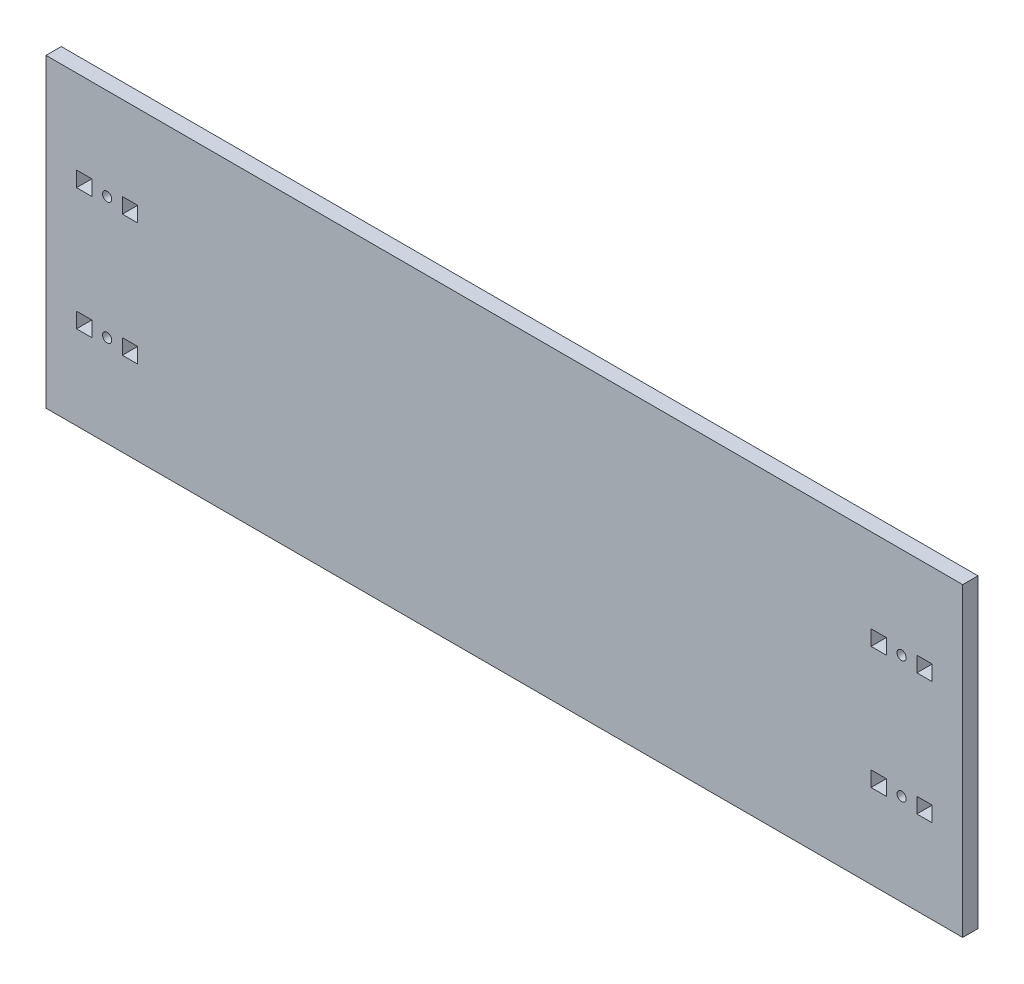
SolidWorks part; units mm, degrees
ref_plane "Front Plane" through (0, 0, 0) normal (0, 0, 1) x (1, 0, 0)
ref_plane "Top Plane" through (0, 0, 0) normal (0, 1, 0) x (1, 0, 0)
ref_plane "Right Plane" through (0, 0, 0) normal (1, 0, 0) x (0, 0, -1)
sketch "Sketch2" plane through (0, 0, 0) normal (0, 0, 1) x (1, 0, 0)
  line L0 (0, 50) -> (300, 50) construction
  line L1 (0, 0) -> (300, 0)
  line L2 (0, 0) -> (0, 100)
  line L3 (0, 100) -> (300, 100)
  line L4 (300, 0) -> (300, 100)
  point P7 (24.4287, 80.3835)
  point P8 (0, 0)
  point P9 (278.3505, 25.351)
  line B0 (15, 70) -> (25, 70) construction
  line B1 (15, 72.5) -> (10, 72.5)
  line B2 (15, 72.5) -> (15, 67.5)
  line B3 (15, 67.5) -> (10, 67.5)
  line B4 (10, 72.5) -> (10, 67.5)
  line B5 (25, 72.5) -> (30, 72.5)
  line B6 (25, 72.5) -> (25, 67.5)
  line B7 (25, 67.5) -> (30, 67.5)
  line B8 (30, 72.5) -> (30, 67.5)
  line B9 (20, 70) -> (20, 76.9724) construction
  circle B10 centre (20, 70) radius 1.5
  line B11 (275, 30) -> (285, 30) construction
  line B12 (275, 32.5) -> (270, 32.5)
  line B13 (275, 32.5) -> (275, 27.5)
  line B14 (275, 27.5) -> (270, 27.5)
  line B15 (270, 32.5) -> (270, 27.5)
  line B16 (285, 32.5) -> (290, 32.5)
  line B17 (285, 32.5) -> (285, 27.5)
  line B18 (285, 27.5) -> (290, 27.5)
  line B19 (290, 32.5) -> (290, 27.5)
  circle B20 centre (280, 30) radius 1.5
  line B21 (15, 30) -> (25, 30) construction
  line B22 (15, 27.5) -> (10, 27.5)
  line B23 (15, 27.5) -> (15, 32.5)
  line B24 (15, 32.5) -> (10, 32.5)
  line B25 (10, 27.5) -> (10, 32.5)
  line B26 (25, 27.5) -> (30, 27.5)
  line B27 (25, 27.5) -> (25, 32.5)
  line B28 (25, 32.5) -> (30, 32.5)
  line B29 (30, 27.5) -> (30, 32.5)
  circle B30 centre (20, 30) radius 1.5
  line B31 (275, 70) -> (285, 70) construction
  line B32 (275, 67.5) -> (270, 67.5)
  line B33 (275, 67.5) -> (275, 72.5)
  line B34 (275, 72.5) -> (270, 72.5)
  line B35 (270, 67.5) -> (270, 72.5)
  line B36 (285, 67.5) -> (290, 67.5)
  line B37 (285, 67.5) -> (285, 72.5)
  line B38 (285, 72.5) -> (290, 72.5)
  line B39 (290, 67.5) -> (290, 72.5)
  line B40 (280, 70) -> (280, 63.0276) construction
  circle B41 centre (280, 70) radius 1.5
  dimension "D1" = 300
  dimension "D2" = 100
  dimension "D3" = 40
  dimension "D4" = 40
  dimension "D5" = 20
  dimension "D6" = 20
sketch_block_instance "Trou M3 plots 5mm-1"
sketch_block "Trou M3 plots 5mm" parameters "D2"=3, "D1"=5, "D3"=5, "D4"=10
sketch_block_instance "Trou M3 plots 5mm-4"
sketch_block_instance "Trou M3 plots 5mm-6"
sketch_block_instance "Trou M3 plots 5mm-7"
extrude "Boss-Extrude1" add sketch "Sketch2" along normal blind 5
